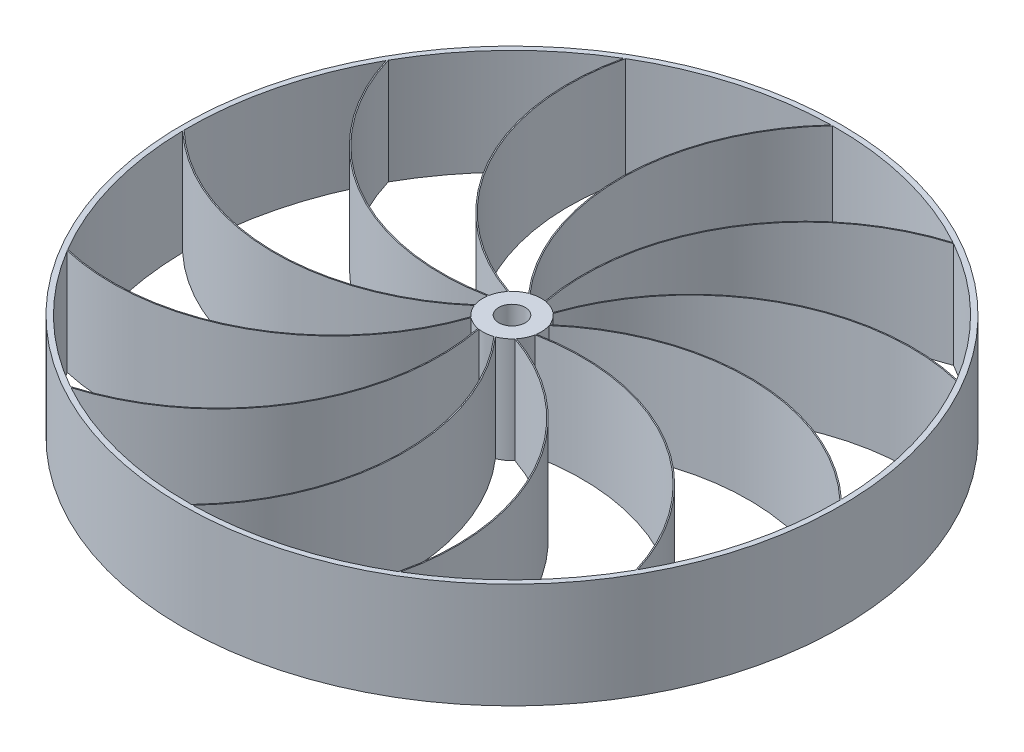
SolidWorks part; units mm, degrees
ref_plane "Front Plane" through (0, 0, 0) normal (0, 0, 1) x (1, 0, 0)
ref_plane "Top Plane" through (0, 0, 0) normal (0, 1, 0) x (1, 0, 0)
ref_plane "Right Plane" through (0, 0, 0) normal (1, 0, 0) x (0, 0, -1)
sketch "Sketch1" plane through (0, 0, 0) normal (0, 1, 0) x (1, 0, 0)
  circle A0 centre (0, 0) radius 2.525
  circle A1 centre (0, 0) radius 62.5
  arc A2 (2.0038, -5.1488) -> (0.9747, -61.4923) centre (-29.75, -32.75) cw
  arc A3 (1.8028, -5.2226) -> (0.6967, -61.4961) centre (-29.75, -32.75) cw
  arc A4 (-0.8391, -5.4609) -> (-29.902, -53.7412) centre (-42.1393, -13.4873) cw
  arc A5 (-1.05, -5.4243) -> (-30.1447, -53.6055) centre (-42.1393, -13.4873) cw
  arc A6 (-3.4571, -4.3097) -> (-52.7665, -31.5902) centre (-43.2373, 9.3893) cw
  arc A7 (-3.6215, -4.1726) -> (-52.9088, -31.3514) centre (-43.2373, 9.3893) cw
  arc A8 (-5.1488, -2.0038) -> (-61.4923, -0.9747) centre (-32.75, 29.75) cw
  arc A9 (-5.2226, -1.8028) -> (-61.4961, -0.6967) centre (-32.75, 29.75) cw
  arc A10 (-5.4609, 0.8391) -> (-53.7412, 29.902) centre (-13.4873, 42.1393) cw
  arc A11 (-5.4243, 1.05) -> (-53.6055, 30.1447) centre (-13.4873, 42.1393) cw
  arc A12 (-4.3097, 3.4571) -> (-31.5902, 52.7665) centre (9.3893, 43.2373) cw
  arc A13 (-4.1726, 3.6215) -> (-31.3514, 52.9088) centre (9.3893, 43.2373) cw
  arc A14 (-2.0038, 5.1488) -> (-0.9747, 61.4923) centre (29.75, 32.75) cw
  arc A15 (-1.8028, 5.2226) -> (-0.6967, 61.4961) centre (29.75, 32.75) cw
  arc A16 (0.8391, 5.4609) -> (29.902, 53.7412) centre (42.1393, 13.4873) cw
  arc A17 (1.05, 5.4243) -> (30.1447, 53.6055) centre (42.1393, 13.4873) cw
  arc A18 (3.4571, 4.3097) -> (52.7665, 31.5902) centre (43.2373, -9.3893) cw
  arc A19 (3.6215, 4.1726) -> (52.9088, 31.3514) centre (43.2373, -9.3893) cw
  arc A20 (5.1488, 2.0038) -> (61.4923, 0.9747) centre (32.75, -29.75) cw
  arc A21 (5.2226, 1.8028) -> (61.4961, 0.6967) centre (32.75, -29.75) cw
  arc A22 (5.4609, -0.8391) -> (53.7412, -29.902) centre (13.4873, -42.1393) cw
  arc A23 (5.4243, -1.05) -> (53.6055, -30.1447) centre (13.4873, -42.1393) cw
  arc A24 (4.3097, -3.4571) -> (31.5902, -52.7665) centre (-9.3893, -43.2373) cw
  arc A25 (4.1726, -3.6215) -> (31.3514, -52.9088) centre (-9.3893, -43.2373) cw
  arc A26 (-29.902, -53.7412) -> (0.6967, -61.4961) centre (0, 0) ccw
  arc A27 (5.4609, -0.8391) -> (5.2226, 1.8028) centre (0, 0) ccw
  arc A28 (-0.1414, -3.1414) -> (-0.1414, -62.3586) centre (-29.75, -32.75) cw construction
  arc A29 (0, -3) -> (0, -62.5) centre (-29.75, -32.75) cw construction
  circle A30 centre (0, 0) radius 61.5 construction
  arc A31 (0.9747, -61.4923) -> (31.3514, -52.9088) centre (0, 0) ccw
  arc A32 (31.5902, -52.7665) -> (53.6055, -30.1447) centre (0, 0) ccw
  arc A33 (53.7412, -29.902) -> (61.4961, 0.6967) centre (0, 0) ccw
  arc A34 (61.4923, 0.9747) -> (52.9088, 31.3514) centre (0, 0) ccw
  arc A35 (52.7665, 31.5902) -> (30.1447, 53.6055) centre (0, 0) ccw
  arc A36 (-0.9747, 61.4923) -> (-31.3514, 52.9088) centre (0, 0) ccw
  arc A37 (-31.5902, 52.7665) -> (-53.6055, 30.1447) centre (0, 0) ccw
  arc A38 (-53.7412, 29.902) -> (-61.4961, -0.6967) centre (0, 0) ccw
  arc A39 (-61.4923, -0.9747) -> (-52.9088, -31.3514) centre (0, 0) ccw
  arc A40 (-52.7665, -31.5902) -> (-30.1447, -53.6055) centre (0, 0) ccw
  circle A41 centre (0, 0) radius 5.525 construction
  arc A42 (5.1488, 2.0038) -> (3.6215, 4.1726) centre (0, 0) ccw
  arc A43 (3.4571, 4.3097) -> (1.05, 5.4243) centre (0, 0) ccw
  arc A44 (0.8391, 5.4609) -> (-1.8028, 5.2226) centre (0, 0) ccw
  arc A45 (-2.0038, 5.1488) -> (-4.1726, 3.6215) centre (0, 0) ccw
  arc A46 (-4.3097, 3.4571) -> (-5.4243, 1.05) centre (0, 0) ccw
  arc A47 (-5.4609, 0.8391) -> (-5.2226, -1.8028) centre (0, 0) ccw
  arc A48 (-5.1488, -2.0038) -> (-3.6215, -4.1726) centre (0, 0) ccw
  arc A49 (-3.4571, -4.3097) -> (-1.05, -5.4243) centre (0, 0) ccw
  arc A50 (-0.8391, -5.4609) -> (1.8028, -5.2226) centre (0, 0) ccw
  arc A51 (2.0038, -5.1488) -> (4.1726, -3.6215) centre (0, 0) ccw
  arc A52 (4.3097, -3.4571) -> (5.4243, -1.05) centre (0, 0) ccw
  arc A53 (29.902, 53.7412) -> (-0.6967, 61.4961) centre (0, 0) ccw
  point P78 (0, 0)
  dimension "D1" = 5.05
  dimension "D2" = 125
  dimension "D3" = 0.2
  dimension "D5" = 1
  dimension "D6" = 3
  dimension "D4" = 12
extrude "Boss-Extrude1" add sketch "Sketch1" along normal blind 20
